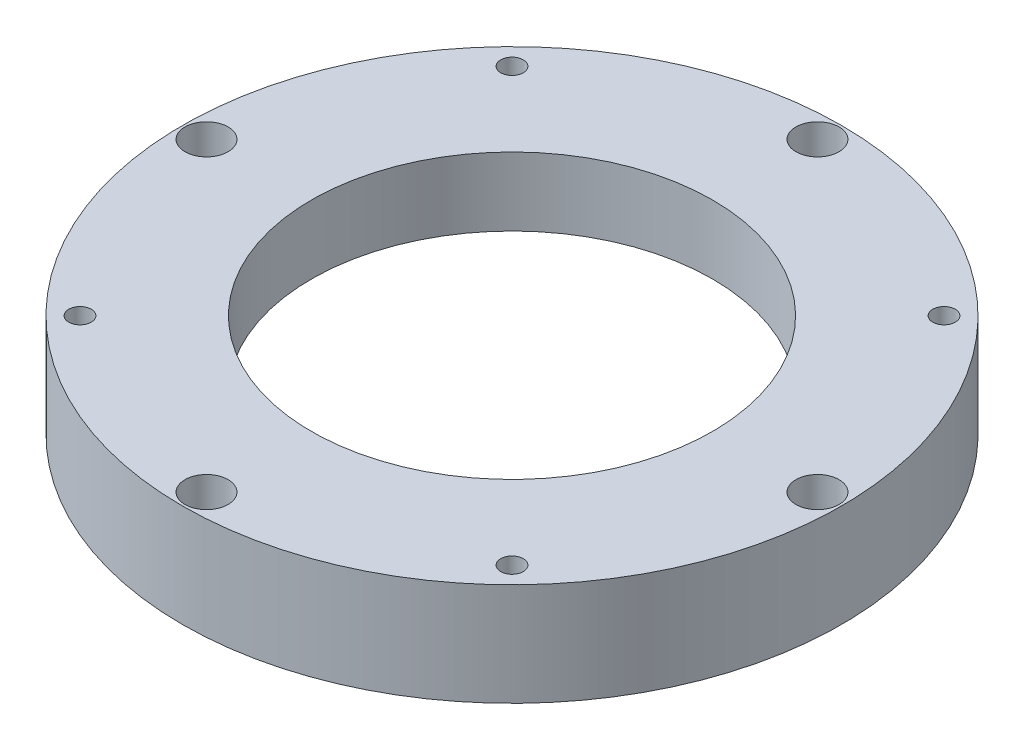
SolidWorks part; units mm, degrees
ref_plane "Front Plane" through (0, 0, 0) normal (0, 0, 1) x (1, 0, 0)
ref_plane "Top Plane" through (0, 0, 0) normal (0, 1, 0) x (1, 0, 0)
ref_plane "Right Plane" through (0, 0, 0) normal (1, 0, 0) x (0, 0, -1)
sketch "Sketch1" plane through (0, 0, 0) normal (0, 1, 0) x (1, 0, 0)
  line L0 (0, 0) -> (42.5, 0) construction
  circle A0 centre (0, 0) radius 45.85
  circle A1 centre (0, 0) radius 27.9
  circle A2 centre (42.5, 0) radius 1.5635
  circle A3 centre (30.052, -30.052) radius 1.5635
  circle A4 centre (0, -42.5) radius 1.5635
  circle A5 centre (0, 0) radius 40.5
  circle A6 centre (-30.052, -30.052) radius 1.5635
  circle A7 centre (-42.5, 0) radius 1.5635
  circle A8 centre (-30.052, 30.052) radius 1.5635
  circle A9 centre (0, 42.5) radius 1.5635
  circle A10 centre (30.052, 30.052) radius 1.5635
  point P13 (0, 0)
  dimension "D1" = 91.7
  dimension "D2" = 55.8
  dimension "D4" = 3.127
  dimension "D6" = 81
  dimension "D3" = 42.5
  dimension "D5" = 8
extrude "Boss-Extrude1" add sketch "Sketch1" against normal blind 4.7625 contours A0 A5 A2 A4 A3 region at (-44.5532, 0, 0)
extrude "Boss-Extrude2" add sketch "Sketch1<4>" along normal blind 4.7625 contours A1 A5 | A0 A5 A2 A4 A3 region at (-44.5532, 0, 0) region at (-39.3545, 0, 0)
sketch "Sketch1<4>" plane through (0, 0, 0) normal (0, 1, 0) x (1, 0, 0) same geometry as "Sketch1"
sketch "Sketch4" plane through (0, 4.7625, 0) normal (0, 1, 0) x (1, 0, 0)
  line L0 (28.4932, -27.352) -> (26.9343, -30.052)
  line L7 (30.052, 33.1697) -> (27.352, 31.6109)
  line L8 (27.352, 31.6109) -> (27.352, 28.4932)
  line L9 (27.352, 28.4932) -> (30.052, 26.9343)
  line L10 (30.052, 26.9343) -> (32.752, 28.4932)
  line L11 (32.752, 28.4932) -> (32.752, 31.6109)
  line L12 (32.752, 31.6109) -> (30.052, 33.1697)
  line L13 (31.6109, -27.352) -> (28.4932, -27.352)
  line L14 (33.1697, -30.052) -> (31.6109, -27.352)
  line L15 (31.6109, -32.752) -> (33.1697, -30.052)
  line L16 (28.4932, -32.752) -> (31.6109, -32.752)
  line L17 (26.9343, -30.052) -> (28.4932, -32.752)
  line L18 (-27.352, -28.4932) -> (-30.052, -26.9343)
  line L19 (-27.352, -31.6109) -> (-27.352, -28.4932)
  line L20 (-30.052, -33.1697) -> (-27.352, -31.6109)
  line L21 (-32.752, -31.6109) -> (-30.052, -33.1697)
  line L22 (-32.752, -28.4932) -> (-32.752, -31.6109)
  line L23 (-30.052, -26.9343) -> (-32.752, -28.4932)
  line L24 (-28.4932, 27.352) -> (-26.9343, 30.052)
  line L25 (-31.6109, 27.352) -> (-28.4932, 27.352)
  line L26 (-33.1697, 30.052) -> (-31.6109, 27.352)
  line L27 (-31.6109, 32.752) -> (-33.1697, 30.052)
  line L28 (-28.4932, 32.752) -> (-31.6109, 32.752)
  line L29 (-26.9343, 30.052) -> (-28.4932, 32.752)
  circle A0 centre (30.052, 30.052) radius 2.7 construction
  point P1 (31.402, 32.3903)
  point P10 (-31.3437, 36.1101)
  point P11 (0, 0)
  point P32 (0, 0)
  dimension "D1" = 5.4
  dimension "D2" = 4
extrude "Cut-Extrude2" cut sketch "Sketch4" against normal blind 4.7625
sketch "Sketch3" plane through (0, 4.7625, 0) normal (0, 1, 0) x (1, 0, 0)
  circle A6 centre (0, -42.5) radius 1.5635 construction
  circle A7 centre (42.5, 0) radius 1.5635 construction
  circle A8 centre (0, 42.5) radius 1.5635 construction
  circle A9 centre (-42.5, 0) radius 1.5635 construction
  circle A10 centre (0, 0) radius 27.9 construction
  circle A11 centre (0, 0) radius 45.85 construction
  circle A12 centre (0, -42.5) radius 1.5635
  circle A13 centre (42.5, 0) radius 1.5635
  circle A14 centre (0, 42.5) radius 1.5635
  circle A15 centre (-42.5, 0) radius 1.5635
  circle A16 centre (0, 0) radius 27.9
  circle A17 centre (0, 0) radius 45.85
  circle A18 centre (0, 42.5) radius 3
  circle A19 centre (42.5, 0) radius 3
  circle A20 centre (0, -42.5) radius 3
  circle A21 centre (-42.5, 0) radius 3
  circle A22 centre (-30.052, 30.052) radius 1.565
  circle A23 centre (30.052, 30.052) radius 1.565
  circle A24 centre (30.052, -30.052) radius 1.565
  circle A25 centre (-30.052, -30.052) radius 1.565
  circle M1 centre (0, 0) radius 27.9
  circle M6 centre (0, 0) radius 45.85
  line M21 (-33.1697, 30.052) -> (-31.6109, 32.752)
  line M22 (-31.6109, 32.752) -> (-28.4932, 32.752)
  line M23 (-28.4932, 32.752) -> (-26.9343, 30.052)
  line M24 (-26.9343, 30.052) -> (-28.4932, 27.352)
  line M25 (-28.4932, 27.352) -> (-31.6109, 27.352)
  line M26 (-31.6109, 27.352) -> (-33.1697, 30.052)
  line M27 (-30.052, -33.1697) -> (-32.752, -31.6109)
  line M28 (-32.752, -31.6109) -> (-32.752, -28.4932)
  line M29 (-32.752, -28.4932) -> (-30.052, -26.9343)
  line M30 (-30.052, -26.9343) -> (-27.352, -28.4932)
  line M31 (-27.352, -28.4932) -> (-27.352, -31.6109)
  line M32 (-27.352, -31.6109) -> (-30.052, -33.1697)
  line M33 (33.1697, -30.052) -> (31.6109, -32.752)
  line M34 (31.6109, -32.752) -> (28.4932, -32.752)
  line M35 (28.4932, -32.752) -> (26.9343, -30.052)
  line M36 (26.9343, -30.052) -> (28.4932, -27.352)
  line M37 (28.4932, -27.352) -> (31.6109, -27.352)
  line M38 (31.6109, -27.352) -> (33.1697, -30.052)
  line M39 (30.052, 33.1697) -> (32.752, 31.6109)
  line M40 (32.752, 31.6109) -> (32.752, 28.4932)
  line M41 (32.752, 28.4932) -> (30.052, 26.9343)
  line M42 (30.052, 26.9343) -> (27.352, 28.4932)
  line M43 (27.352, 28.4932) -> (27.352, 31.6109)
  line M44 (27.352, 31.6109) -> (30.052, 33.1697)
  dimension "D1" = 6
  dimension "D2" = 3.13
extrude "Boss-Extrude3" add sketch "Sketch3" along normal blind 4.7625 contours A21 A20 A19 A18 M6 M1 M44 M39 M40 M41 M42 M43 M38 M33 M34 M35 M36 M37 M32 M27 M28 M29 M30 M31 M26 M21 M22 M23 M24 M25 | A22 M21 M26 M25 M24 M23 M22 | A23 M39 M44 M43 M42 M41 M40 | A24 M33 M38 M37 M36 M35 M34 | A25 M27 M32 M31 M30 M29 M28 region at (-45.7203, 4.7625, 0) region at (-32.3189, 4.7625, -31.3608) region at (-31.3608, 4.7625, 32.3189) region at (32.3189, 4.7625, 31.3608) region at (31.3608, 4.7625, -32.3189)
sketch "Sketch5" plane through (0, 9.525, 0) normal (0, 1, 0) x (1, 0, 0)
  line L0 (0, 0) -> (30.052, 30.052) construction
  circle A0 centre (0, 42.5) radius 3 construction
  circle A1 centre (30.052, 30.052) radius 1.565 construction
  circle A2 centre (42.5, 0) radius 3 construction
  circle A3 centre (30.052, -30.052) radius 1.565 construction
  circle A4 centre (0, -42.5) radius 3 construction
  circle A5 centre (-30.052, -30.052) radius 1.565 construction
  circle A6 centre (-42.5, 0) radius 3 construction
  circle A7 centre (-30.052, 30.052) radius 1.565 construction
  circle A8 centre (0, 0) radius 45.85 construction
  circle A9 centre (0, 0) radius 27.9 construction
  circle A10 centre (0, 42.5) radius 3
  circle A11 centre (30.052, 30.052) radius 1.565
  circle A12 centre (42.5, 0) radius 3
  circle A13 centre (30.052, -30.052) radius 1.565
  circle A14 centre (0, -42.5) radius 3
  circle A15 centre (-30.052, -30.052) radius 1.565
  circle A16 centre (-42.5, 0) radius 3
  circle A17 centre (-30.052, 30.052) radius 1.565
  circle A18 centre (0, 0) radius 45.85
  circle A19 centre (0, 0) radius 27.9
  arc A20 (6.31, 31.2697) -> (18.4511, 26.0224) centre (0, 0) cw
  arc A21 (4.6718, 37.2871) -> (6.4423, 39.762) centre (0, 42.5) ccw
  arc A22 (24.5734, 31.0284) -> (24.5119, 29.527) centre (30.052, 30.052) ccw
  arc A23 (24.5119, 29.527) -> (18.4511, 26.0224) centre (20.6784, 29.1636) cw
  arc A24 (4.6718, 37.2871) -> (6.31, 31.2697) centre (7, 34.6892) ccw
  arc A25 (22.8162, 35.0834) -> (24.5734, 31.0284) centre (20.6354, 31.7302) cw
  arc A26 (8.6987, 40.936) -> (6.4423, 39.762) centre (8.283, 38.9797) ccw
  arc A27 (22.8162, 35.0834) -> (8.6987, 40.936) centre (0, 0) ccw
  arc A28 (35.0834, 22.8162) -> (31.0284, 24.5734) centre (31.7302, 20.6354) ccw
  arc A29 (31.0284, 24.5734) -> (29.527, 24.5119) centre (30.052, 30.052) cw
  arc A30 (29.527, 24.5119) -> (26.0224, 18.4511) centre (29.1636, 20.6784) ccw
  arc A31 (31.2697, 6.31) -> (26.0224, 18.4511) centre (0, 0) ccw
  arc A32 (35.0834, 22.8162) -> (40.936, 8.6987) centre (0, 0) cw
  arc A33 (40.936, 8.6987) -> (39.762, 6.4423) centre (38.9797, 8.283) cw
  arc A34 (37.2871, 4.6718) -> (39.762, 6.4423) centre (42.5, 0) cw
  arc A35 (37.2871, 4.6718) -> (31.2697, 6.31) centre (34.6892, 7) cw
  arc A36 (37.2871, -4.6718) -> (31.2697, -6.31) centre (34.6892, -7) ccw
  arc A37 (31.2697, -6.31) -> (26.0224, -18.4511) centre (0, 0) cw
  arc A38 (29.527, -24.5119) -> (26.0224, -18.4511) centre (29.1636, -20.6784) cw
  arc A39 (31.0284, -24.5734) -> (29.527, -24.5119) centre (30.052, -30.052) ccw
  arc A40 (35.0834, -22.8162) -> (31.0284, -24.5734) centre (31.7302, -20.6354) cw
  arc A41 (35.0834, -22.8162) -> (40.936, -8.6987) centre (0, 0) ccw
  arc A42 (40.936, -8.6987) -> (39.762, -6.4423) centre (38.9797, -8.283) ccw
  arc A43 (37.2871, -4.6718) -> (39.762, -6.4423) centre (42.5, 0) ccw
  arc A44 (24.5119, -29.527) -> (18.4511, -26.0224) centre (20.6784, -29.1636) ccw
  arc A45 (24.5734, -31.0284) -> (24.5119, -29.527) centre (30.052, -30.052) cw
  arc A46 (22.8162, -35.0834) -> (24.5734, -31.0284) centre (20.6354, -31.7302) ccw
  arc A47 (22.8162, -35.0834) -> (8.6987, -40.936) centre (0, 0) cw
  arc A48 (6.31, -31.2697) -> (18.4511, -26.0224) centre (0, 0) ccw
  arc A49 (4.6718, -37.2871) -> (6.31, -31.2697) centre (7, -34.6892) cw
  arc A50 (4.6718, -37.2871) -> (6.4423, -39.762) centre (0, -42.5) cw
  arc A51 (8.6987, -40.936) -> (6.4423, -39.762) centre (8.283, -38.9797) cw
  arc A52 (-4.6718, -37.2871) -> (-6.31, -31.2697) centre (-7, -34.6892) ccw
  arc A53 (-6.31, -31.2697) -> (-18.4511, -26.0224) centre (0, 0) cw
  arc A54 (-24.5119, -29.527) -> (-18.4511, -26.0224) centre (-20.6784, -29.1636) cw
  arc A55 (-24.5734, -31.0284) -> (-24.5119, -29.527) centre (-30.052, -30.052) ccw
  arc A56 (-22.8162, -35.0834) -> (-24.5734, -31.0284) centre (-20.6354, -31.7302) cw
  arc A57 (-22.8162, -35.0834) -> (-8.6987, -40.936) centre (0, 0) ccw
  arc A58 (-8.6987, -40.936) -> (-6.4423, -39.762) centre (-8.283, -38.9797) ccw
  arc A59 (-4.6718, -37.2871) -> (-6.4423, -39.762) centre (0, -42.5) ccw
  arc A60 (-29.527, -24.5119) -> (-26.0224, -18.4511) centre (-29.1636, -20.6784) ccw
  arc A61 (-31.0284, -24.5734) -> (-29.527, -24.5119) centre (-30.052, -30.052) cw
  arc A62 (-35.0834, -22.8162) -> (-31.0284, -24.5734) centre (-31.7302, -20.6354) ccw
  arc A63 (-35.0834, -22.8162) -> (-40.936, -8.6987) centre (0, 0) cw
  arc A64 (-31.2697, -6.31) -> (-26.0224, -18.4511) centre (0, 0) ccw
  arc A65 (-37.2871, -4.6718) -> (-31.2697, -6.31) centre (-34.6892, -7) cw
  arc A66 (-37.2871, -4.6718) -> (-39.762, -6.4423) centre (-42.5, 0) cw
  arc A67 (-40.936, -8.6987) -> (-39.762, -6.4423) centre (-38.9797, -8.283) cw
  arc A68 (-37.2871, 4.6718) -> (-31.2697, 6.31) centre (-34.6892, 7) ccw
  arc A69 (-31.2697, 6.31) -> (-26.0224, 18.4511) centre (0, 0) cw
  arc A70 (-29.527, 24.5119) -> (-26.0224, 18.4511) centre (-29.1636, 20.6784) cw
  arc A71 (-31.0284, 24.5734) -> (-29.527, 24.5119) centre (-30.052, 30.052) ccw
  arc A72 (-35.0834, 22.8162) -> (-31.0284, 24.5734) centre (-31.7302, 20.6354) cw
  arc A73 (-35.0834, 22.8162) -> (-40.936, 8.6987) centre (0, 0) ccw
  arc A74 (-40.936, 8.6987) -> (-39.762, 6.4423) centre (-38.9797, 8.283) ccw
  arc A75 (-37.2871, 4.6718) -> (-39.762, 6.4423) centre (-42.5, 0) ccw
  arc A76 (-24.5119, 29.527) -> (-18.4511, 26.0224) centre (-20.6784, 29.1636) ccw
  arc A77 (-24.5734, 31.0284) -> (-24.5119, 29.527) centre (-30.052, 30.052) cw
  arc A78 (-22.8162, 35.0834) -> (-24.5734, 31.0284) centre (-20.6354, 31.7302) ccw
  arc A79 (-22.8162, 35.0834) -> (-8.6987, 40.936) centre (0, 0) cw
  arc A80 (-6.31, 31.2697) -> (-18.4511, 26.0224) centre (0, 0) ccw
  arc A81 (-4.6718, 37.2871) -> (-6.31, 31.2697) centre (-7, 34.6892) cw
  arc A82 (-4.6718, 37.2871) -> (-6.4423, 39.762) centre (0, 42.5) cw
  arc A83 (-8.6987, 40.936) -> (-6.4423, 39.762) centre (-8.283, 38.9797) cw
  point P137 (0, 0)
  dimension "D1" = 4
  dimension "D2" = 4
  dimension "D3" = 4
  dimension "D4" = 4
  dimension "D5" = 12
  dimension "D8" = 2
  dimension "D9" = 4
  dimension "D7" = 14
  dimension "D6" = 4
extrude "Cut-Extrude3" [suppressed] cut sketch "Sketch5" against normal blind 4.7625 contours A75 A68 A69 A70 A71 A72 A73 A74 | A83 A79 A78 A77 A76 A80 A81 A82 | A25 A27 A26 A21 A24 A20 A23 A22 | A35 A34 A33 A32 A28 A29 A30 A31 | A43 A36 A37 A38 A39 A40 A41 A42 | A51 A47 A46 A45 A44 A48 A49 A50 | A59 A52 A53 A54 A55 A56 A57 A58 | A67 A63 A62 A61 A60 A64 A65 A66
equation "\"bearing_21_OD\"= 21mm"
equation "\"pin_cirlce_diameter\"= 75mm"
equation "\"pin_diam\"= 6mm"
equation "\"gear_thickness\"= 4mm"
equation "\"ball_bearing_diam\"= 3.214mm"
equation "\"bearing_21_outer_clearance\"= 0.127mm'change this"
equation "\"bearing_15_OD\"= 15mm"
equation "\"bearing_15_outer_clearance\"= 0mm'change this"
equation "\"thrust_bearing_thickness\"= 5mm'measure this irl and change"
equation "\"D1@Boss-Extrude1\"=\"sheetThickness\""
equation "\"largeBearOD\"= 21mm"
equation "\"largeBearID\" = 15mm"
equation "\"largeBearOTight\"= 0.34375mm'calibrate - hold onto gears"
equation "\"largeBearITight\"= 0mm'calibrate - hold onto eccentric nut"
equation "\"largeBearFlangeDiam\" = 22.5mm"
equation "\"largeBearFlangeWidth\" = 0.8mm"
equation "\"smallBearOD\"= 14.8mm"
equation "\"smallBearOTight\"= 0mm'calibrate - hold onto bottom of gearbox"
equation "\"smallBearOLoose\"= 0mm'calibrate - able to take off topHat"
equation "\"smallBearID\" = 10mm"
equation "\"smallBearITight\" = 0mm'hold onto "
equation "\"pinCircleDiam\"= 75mm"
equation "\"pinDiam\"= 6mm"
equation "\"sheetThickness\"= 0.1875in"
equation "\"ballBearDiam\"= 3.5mm"
equation "\"thrustBearingThickness\"= 5mm'measure this irl and change"
equation "\"thrustBearingID\"= 0mm'measure this irl and change"
equation "\"thrustBearingOD\"= 0mm'measure this irl and change"
equation "\"eccentricity\" = 1mm"
equation "\"D1@Boss-Extrude2\"=\"sheetThickness\""
equation "\"D1@Boss-Extrude3\"=\"sheetThickness\""
equation "\"D1@Cut-Extrude2\"=\"sheetThickness\""
equation "\"D1@Cut-Extrude3\"=\"sheetThickness\""
